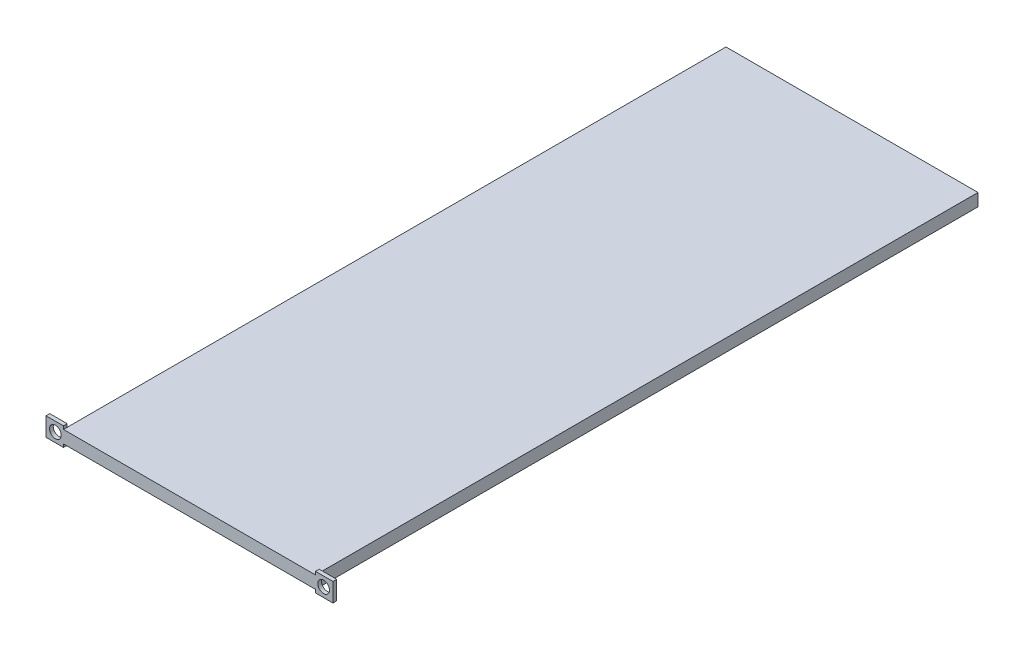
SolidWorks part; units mm, degrees
ref_plane "Front Plane" through (0, 0, 0) normal (0, 0, 1) x (1, 0, 0)
ref_plane "Top Plane" through (0, 0, 0) normal (0, 1, 0) x (1, 0, 0)
ref_plane "Right Plane" through (0, 0, 0) normal (1, 0, 0) x (0, 0, -1)
sketch "Sketch1" plane through (0, 0, 0) normal (0, 0, 1) x (1, 0, 0)
  line L1 (0, 0) -> (202, 0)
  line L2 (0, 0) -> (0, 10)
  line L3 (0, 10) -> (202, 10)
  line L4 (202, 0) -> (202, 10)
  dimension "D1" = 202
  dimension "D2" = 10
extrude "Boss-Extrude1" add sketch "Sketch1" along normal blind 531
sketch "Sketch2" plane through (0, 0, 0) normal (-1, 0, 0) x (0, 0, 1)
  line L0 (531, 10) -> (531, 0) construction
  line L1 (531, 12.5) -> (528, 12.5)
  line L2 (531, 12.5) -> (531, -2.5)
  line L3 (531, -2.5) -> (528, -2.5)
  line L4 (528, 12.5) -> (528, -2.5)
  dimension "D1" = 3
  dimension "D2" = 15
  dimension "D3" = 2.5
extrude "Boss-Extrude2" add sketch "Sketch2" along normal blind 14
sketch "Sketch4" plane through (202, 0, 0) normal (1, 0, 0) x (0, 0, -1)
  line L1 (-531, 12.5) -> (-528, 12.5)
  line L2 (-531, 12.5) -> (-531, -2.5)
  line L3 (-531, -2.5) -> (-528, -2.5)
  line L4 (-528, 12.5) -> (-528, -2.5)
extrude "Boss-Extrude3" add sketch "Sketch4" along normal blind 14
sketch "Sketch3" plane through (0, 0, 528) normal (0, 0, -1) x (-1, 0, 0)
  line L0 (0, 10) -> (0, 0) construction
  line L1 (-101, 36.0752) -> (-101, -22.8304) construction
  circle A0 centre (6.5, 5) radius 4.7
  circle A1 centre (-208.5, 5) radius 4.7
  dimension "D1" = 9.4
  dimension "D2" = 6.5
  dimension "D3" = 5
  dimension "D4" = 101
extrude "Cut-Extrude1" cut sketch "Sketch3" against normal blind 13
